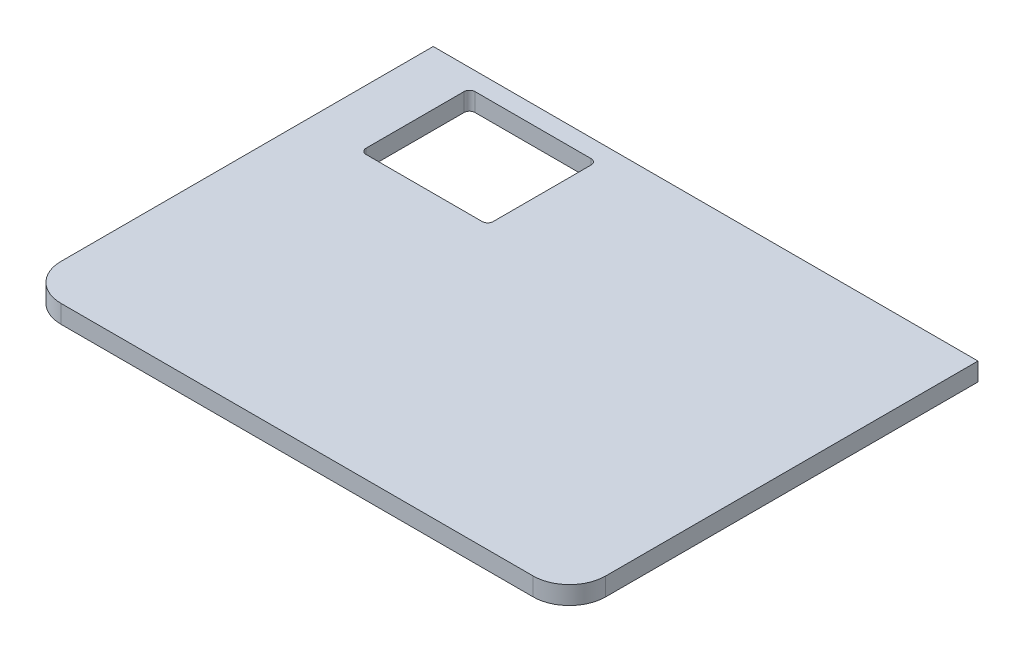
SolidWorks part; units mm, degrees
ref_plane "Ebene vorne" through (0, 0, 0) normal (0, 0, 1) x (1, 0, 0)
ref_plane "Ebene oben" through (0, 0, 0) normal (0, 1, 0) x (1, 0, 0)
ref_plane "Ebene rechts" through (0, 0, 0) normal (1, 0, 0) x (0, 0, -1)
sketch "Skizze1" plane through (0, 0, 0) normal (0, 1, 0) x (1, 0, 0)
  line L0 (150, 75) -> (150, 150)
  line L1 (0, -75) -> (150, -75)
  line L2 (0, -75) -> (0, 75)
  line L3 (150, 150) -> (0, 150)
  line L4 (150, -75) -> (150, 75)
  line L5 (0, 150) -> (0, 75)
  line L6 (0, 0) -> (150, 0) construction
  dimension "D1" = 150
  dimension "D2" = 75
extrude "Linear austragen1" add sketch "Skizze1" along normal blind 10
fillet "Verrundung1" radius 20 1 edges at (150, 5, 75)
mirror "Spiegeln2" about plane through (0, 10, -150) normal (1, 0, 0) of "Verrundung1", "Linear austragen1"
sketch "Skizze3" plane through (0, 0, 0) normal (0, 1, 0) x (-1, 0, 0)
  line L1 (120, -140) -> (50, -140)
  line L2 (120, -140) -> (120, -80)
  line L3 (120, -80) -> (50, -80)
  line L4 (50, -140) -> (50, -80)
  line L8 (150, 55) -> (150, -150) construction
  line L9 (-150, -150) -> (150, -150) construction
  dimension "D1" = 30
  dimension "D2" = 10
  dimension "D3" = 70
  dimension "D4" = 60
extrude "Schnitt-Linear austragen1" cut sketch "Skizze3" along normal through all
fillet "Verrundung2" radius 3 4 edges at (-120, 5, -80) (-50, 5, -80) (-120, 5, -140) (-50, 5, -140)
